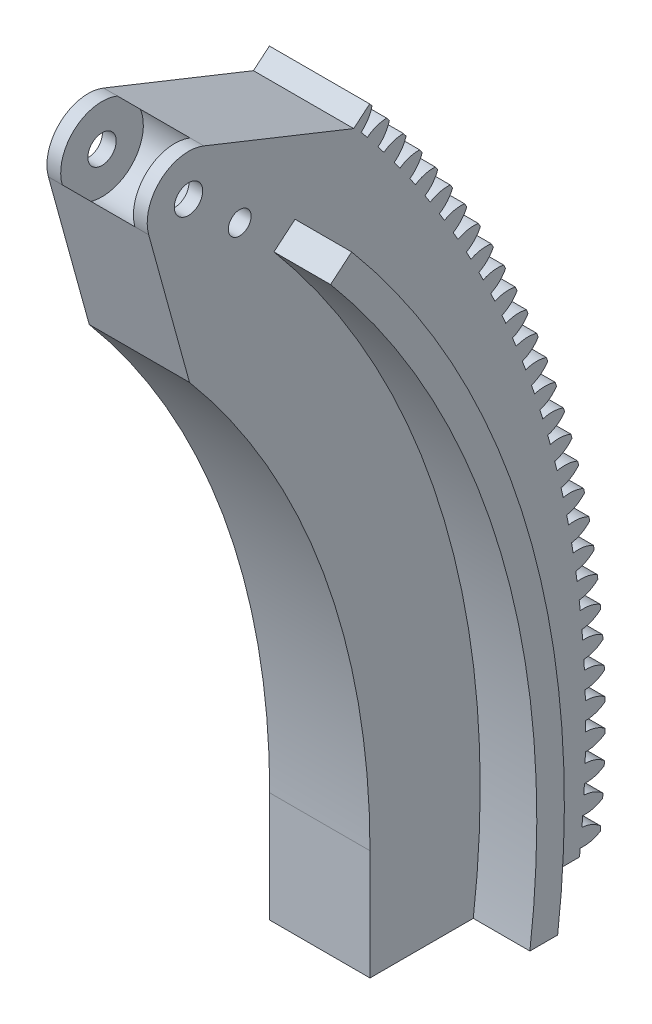
SolidWorks part; units mm, degrees
material "ABS"
ref_plane "Front Plane" through (0, 0, 0) normal (0, 0, 1) x (1, 0, 0)
ref_plane "Top Plane" through (0, 0, 0) normal (0, 1, 0) x (1, 0, 0)
ref_plane "Right Plane" through (0, 0, 0) normal (1, 0, 0) x (0, 0, -1)
ref_plane "idk" through (6.35, 0, 0) normal (1, 0, 0) x (0, 0, -1)
sketch "Sketch1" plane through (0, 0, 0) normal (1, 0, 0) x (0, 0, -1)
  line L0 (-1000, 0) -> (177.8, 0) construction
  line L1 (177.8, 0) -> (177.8, -25.4)
  line L2 (0, 0) -> (136.2027, 114.2876) construction
  line L4 (227.2, 0) -> (49000, 0) construction
  line L7 (177.8, -25.4) -> (227.2, -25.4) construction
  line L8 (227.2, 0) -> (227.2, -25.4) construction
  line L10 (-1.0719, -0.8495) -> (179.1555, 141.9904) construction
  line L61 (181.0098, 139.6187) -> (0, 0) construction
  line L62 (136.2027, 114.2876) -> (126.7844, 148.4774)
  line L64 (177.8, -25.4) -> (225.7757, -25.4)
  line L65 (136.2027, 114.2876) -> (155.124, 130.1645) construction
  line L66 (155.124, 130.1645) -> (174.0453, 146.0413) construction
  line L68 (0, 0) -> (35966.99, 34732.9185) construction
  line L69 (178.0587, 141.1212) -> (178.0836, 141.1409) construction
  line L70 (0, 0) -> (135.9673, 151.007) construction
  line L71 (139.5033, 159.8514) -> (174.0453, 146.0413)
  arc A2 (177.8, 0) -> (136.2027, 114.2876) centre (0, 0) ccw
  circle A19 centre (0, 0) radius 228.6 construction
  arc A22 (174.0453, 146.0413) -> (227.2, 0) centre (0, 0) cw
  arc A23 (227.2, 0) -> (225.7757, -25.4) centre (0, 0) cw
  arc A24 (126.7844, 148.4774) -> (139.5033, 159.8514) centre (135.9673, 151.007) cw
  point P6 (178.0836, 141.1409)
  point P7 (136.2027, 114.2876)
  dimension "D1" = 177.8
  dimension "D2" = 6.35
  dimension "D12" = 457.2
  dimension "D8" = 9.525
  dimension "D3" = 40
  dimension "D4" = 49.4
  dimension "D5" = 25.4
  dimension "D6" = 203.2
  dimension "D7" = 48
  dimension "D13" = 44
sketch "Sketch2" plane through (6.35, 0, 0) normal (1, 0, 0) x (0, 0, -1)
  line L0 (0, 0) -> (165.1, 0) construction
  line L1 (165.1, 0) -> (190.5, 0) construction
  line L2 (0, 0) -> (49240.3877, 8682.4089) construction
  circle A0 centre (165.1, 0) radius 3.2639
  circle A1 centre (190.5, 0) radius 3.2639
  arc A3 (165.1, 0) -> (162.5918, 28.6693) centre (0, 0) ccw construction
  circle A4 centre (162.5918, 28.6693) radius 3.2639
  arc A5 (190.5, 0) -> (187.6059, 33.08) centre (0, 0) ccw construction
  circle A6 centre (187.6059, 33.08) radius 3.2639
  dimension "D3" = 6.5278
  dimension "D4" = 6.5278
  dimension "D6" = 6.5278
  dimension "D7" = 6.5278
  dimension "D1" = 165.1
  dimension "D2" = 25.4
  dimension "D5" = 10
sketch "Sketch11" plane through (6.35, 0, 0) normal (1, 0, 0) x (0, 0, -1)
  line L0 (-785.502, -659.1144) -> (0, 0) construction
  line L2 (-1000, 0) -> (0, 0) construction
  line L4 (155.6602, 130.6144) -> (177.7223, 149.1267)
  line L5 (177.7223, 149.1267) -> (921.7047, 773.4021) construction
  line L6 (232, 0) -> (232, -25.4) construction
  line L7 (232, -25.4) -> (222.9391, -25.4) construction
  line L8 (201.6062, -25.4) -> (230.6054, -25.4)
  line L9 (203.2, 0) -> (232, 0) construction
  arc A0 (-230, 0) -> (-176.1902, -147.8412) centre (0, 0) ccw construction
  arc A1 (-232, 0) -> (-177.7223, -149.1267) centre (0, 0) ccw construction
  arc A2 (-229.6, 0) -> (-175.8838, -147.584) centre (0, 0) ccw construction
  arc A3 (232, 0) -> (177.7223, 149.1267) centre (0, 0) ccw
  arc A4 (230, 0) -> (176.1902, 147.8412) centre (0, 0) ccw construction
  arc A5 (-229.6, 0) -> (-175.8838, -147.584) centre (0, 0) ccw
  arc A6 (155.6602, 130.6144) -> (203.2, 0) centre (0, 0) cw
  arc A7 (232, 0) -> (230.6054, -25.4) centre (0, 0) cw
  arc A8 (203.2, 0) -> (201.6062, -25.4) centre (0, 0) cw
  dimension "D1" = 460
  dimension "D2" = 464
  dimension "D4" = 203.2
  dimension "D3" = 2.4
  dimension "D6" = 25.4
extrude "Teeth blank" add sketch "Sketch11" against normal blind 6.35 contours A3 L4 region at (6.35, 60.7212, -203.0048)
sketch "Sketch12" plane through (6.35, 0, 0) normal (1, 0, 0) x (0, 0, -1)
  line L0 (0, 0) -> (232, 0) construction
  line L2 (229.9946, 1.5708) -> (229.9946, -1.5708) construction
  line L3 (0, 0) -> (227.4972, 1.1241) construction
  line L4 (225.6789, 0) -> (232.9848, 2.6591) construction
  line L5 (0, 0) -> (232.9783, 3.1825) construction
  line L6 (229.9946, 1.5708) -> (229.9517, 4.7121) construction
  circle A0 centre (0, 0) radius 230 construction
  arc A1 (230.6054, -25.4) -> (177.7223, 149.1267) centre (0, 0) ccw construction
  circle A2 centre (0, 0) radius 227.5 construction
  arc A3 (227.4972, 1.1241) -> (232.9725, 3.5819) centre (227.4606, 8.5329) ccw
  arc A4 (231.5994, -25.5095) -> (232.9725, -3.5819) centre (0, 0) cw construction
  arc A5 (227.4972, -1.1241) -> (232.9725, -3.5819) centre (227.4606, -8.5329) cw
  arc A6 (231.5994, -25.5095) -> (178.4884, 149.7695) centre (0, 0) ccw
  arc A7 (231.5994, -25.5095) -> (232.9725, 3.5819) centre (0, 0) ccw construction
  arc A8 (227.4972, 1.1241) -> (227.4972, -1.1241) centre (0, 0) cw
  arc A9 (230.6054, -25.4) -> (177.7223, 149.1267) centre (0, 0) ccw construction
  arc A10 (232.9725, 3.5819) -> (232.9725, -3.5819) centre (0, 0) cw
  dimension "D1" = 460
  dimension "D3" = 20
  dimension "D4" = 0.783
  dimension "D5" = 4.5
  dimension "D2" = 1
extrude "Primary blank" add sketch "Sketch1" along normal blind 29.464
extrude "Tooth cut" cut sketch "Sketch12" against normal blind 6.35
pattern_circular "Tooth pattern" count 230 every 1.565 about axis through (0, 0, 0) along (1, 0, 0) of "Tooth cut"
sketch "Sketch15" plane through (6.35, 0, 0) normal (1, 0, 0) x (0, 0, -1)
  line L0 (0, 0) -> (135.9673, 151.007) construction
  line L2 (0, 0) -> (102.4673, 0) construction
  circle A0 centre (135.9673, 151.007) radius 3.2639
  dimension "D3" = 6.5278
  dimension "D1" = 203.2
  dimension "D2" = 48
extrude "Holes for top support" cut sketch "Sketch15" against normal through all both and the other way through all
sketch "Sketch22" plane through (6.35, 0, 0) normal (1, 0, 0) x (0, 0, -1)
  line L0 (0, 0) -> (135.9673, 151.007)
  line L1 (0, 0) -> (177.8, 0)
  dimension "D1" = 177.8
sketch "Sketch23" plane through (0, 0, 0) normal (1, 0, 0) x (0, 0, -1)
  line L0 (0, 0) -> (177.8, 0) construction
  line L1 (0, 0) -> (136.2027, 114.2876) construction
  line L2 (177.8, 0) -> (196.85, 0) construction
  line L3 (136.2027, 114.2876) -> (155.6602, 130.6144) construction
  line L5 (155.6602, 130.6144) -> (160.5246, 134.6961)
  line L7 (201.6062, -25.4) -> (0, 0) construction
  line L8 (208.0049, -25.4) -> (201.6062, -25.4)
  line L9 (177.8, -25.4) -> (226.0776, -25.4) construction
  arc A0 (177.8, 0) -> (136.2027, 114.2876) centre (0, 0) ccw construction
  circle A2 centre (196.85, 0) radius 6.35 construction
  arc A3 (203.2, 0) -> (155.6602, 130.6144) centre (0, 0) ccw
  arc A4 (209.55, 0) -> (160.5246, 134.6961) centre (0, 0) ccw
  circle A5 centre (215.9, 0) radius 6.35 construction
  arc A6 (203.2, 0) -> (201.6062, -25.4) centre (0, 0) cw
  arc A7 (209.55, 0) -> (208.0049, -25.4) centre (0, 0) cw
  dimension "D4" = 6.35
  dimension "D5" = 12.7
  dimension "D6" = 12.7
  dimension "D1" = 177.8
  dimension "D2" = 40
  dimension "D3" = 19.05
extrude "Thing to slide along bearings" add sketch "Sketch23" against normal blind 9.8742
ref_plane "Mirror plane" through (14.732, 0, 0) normal (1, 0, 0) x (0, 0, -1)
mirror "Mirroring slider" about plane through (14.732, 0, 0) normal (1, 0, 0) of "Thing to slide along bearings"
sketch "Sketch27" plane through (6.35, 0, 0) normal (1, 0, 0) x (0, 0, -1)
  line L2 (177.7223, 149.1267) -> (174.0453, 146.0413)
  line L3 (177.7223, 149.1267) -> (174.0453, 146.0413)
  line L7 (225.7757, -25.4) -> (226.0776, -25.4)
  line L8 (225.7757, -25.4) -> (226.0776, -25.4)
  arc A4 (227.2191, 11.3011) -> (227.0964, 13.5458) centre (0, 0) ccw
  arc A95 (231.8253, 9.0012) -> (231.7841, 10.0069) centre (0, 0) ccw
  arc A111 (227.3816, 7.3377) -> (231.8253, 9.0012) centre (227.1427, 14.7428) ccw
  arc A112 (227.3816, 7.3377) -> (231.8253, 9.0012) centre (227.1427, 14.7428) ccw
  arc A113 (231.7841, 10.0069) -> (227.2191, 11.3011) centre (227.5872, 3.9012) ccw
  arc A114 (231.7841, 10.0069) -> (227.2191, 11.3011) centre (227.5872, 3.9012) ccw
  arc A139 (227.2191, 11.3011) -> (227.0964, 13.5458) centre (0, 0) ccw
  arc A141 (227.0964, 13.5458) -> (231.493, 15.3301) centre (226.6552, 20.9417) ccw
  arc A143 (227.0964, 13.5458) -> (231.493, 15.3301) centre (226.6552, 20.9417) ccw
  arc A145 (231.493, 15.3301) -> (231.4243, 16.3343) centre (0, 0) ccw
  arc A147 (231.493, 15.3301) -> (231.4243, 16.3343) centre (0, 0) ccw
  arc A149 (231.4243, 16.3343) -> (226.8257, 17.5033) centre (227.3957, 10.1163) ccw
  arc A151 (231.4243, 16.3343) -> (226.8257, 17.5033) centre (227.3957, 10.1163) ccw
  arc A153 (226.8257, 17.5033) -> (226.6416, 19.7439) centre (0, 0) ccw
  arc A155 (226.8257, 17.5033) -> (226.6416, 19.7439) centre (0, 0) ccw
  arc A157 (226.6416, 19.7439) -> (230.9878, 21.6476) centre (225.9986, 27.1249) ccw
  arc A159 (226.6416, 19.7439) -> (230.9878, 21.6476) centre (225.9986, 27.1249) ccw
  arc A161 (230.9878, 21.6476) -> (230.8918, 22.6495) centre (0, 0) ccw
  arc A163 (230.9878, 21.6476) -> (230.8918, 22.6495) centre (0, 0) ccw
  arc A165 (230.8918, 22.6495) -> (226.2629, 23.6925) centre (227.0345, 16.3238) ccw
  arc A167 (230.8918, 22.6495) -> (226.2629, 23.6925) centre (227.0345, 16.3238) ccw
  arc A169 (226.2629, 23.6925) -> (226.0178, 25.9272) centre (0, 0) ccw
  arc A171 (226.2629, 23.6925) -> (226.0178, 25.9272) centre (0, 0) ccw
  arc A173 (226.0178, 25.9272) -> (230.3104, 27.9489) centre (225.1734, 33.2879) ccw
  arc A175 (226.0178, 25.9272) -> (230.3104, 27.9489) centre (225.1734, 33.2879) ccw
  arc A177 (230.3104, 27.9489) -> (230.1869, 28.9478) centre (0, 0) ccw
  arc A179 (230.3104, 27.9489) -> (230.1869, 28.9478) centre (0, 0) ccw
  arc A181 (230.1869, 28.9478) -> (225.5314, 29.8639) centre (226.5039, 22.5191) ccw
  arc A182 (230.1869, 28.9478) -> (225.5314, 29.8639) centre (226.5039, 22.5191) ccw
  arc A184 (225.5314, 29.8639) -> (225.2252, 32.0911) centre (0, 0) ccw
  arc A186 (225.5314, 29.8639) -> (225.2252, 32.0911) centre (0, 0) ccw
  arc A189 (231.8253, 9.0012) -> (231.7841, 10.0069) centre (0, 0) ccw
  arc A282 (225.2252, 32.0911) -> (229.461, 34.2294) centre (224.1801, 39.426) ccw
  arc A284 (225.2252, 32.0911) -> (229.461, 34.2294) centre (224.1801, 39.426) ccw
  arc A286 (229.461, 34.2294) -> (229.3104, 35.2245) centre (0, 0) ccw
  arc A288 (229.461, 34.2294) -> (229.3104, 35.2245) centre (0, 0) ccw
  arc A290 (229.3104, 35.2245) -> (224.6315, 36.0131) centre (225.8043, 28.6976) ccw
  arc A292 (229.3104, 35.2245) -> (224.6315, 36.0131) centre (225.8043, 28.6976) ccw
  arc A294 (224.6315, 36.0131) -> (224.2647, 38.2311) centre (0, 0) ccw
  arc A296 (224.6315, 36.0131) -> (224.2647, 38.2311) centre (0, 0) ccw
  arc A298 (224.2647, 38.2311) -> (228.4404, 40.4843) centre (223.0196, 45.5347) ccw
  arc A300 (224.2647, 38.2311) -> (228.4404, 40.4843) centre (223.0196, 45.5347) ccw
  arc A302 (228.4404, 40.4843) -> (228.2626, 41.4749) centre (0, 0) ccw
  arc A304 (228.4404, 40.4843) -> (228.2626, 41.4749) centre (0, 0) ccw
  arc A306 (228.2626, 41.4749) -> (223.564, 42.1355) centre (224.9362, 34.8547) ccw
  arc A308 (228.2626, 41.4749) -> (223.564, 42.1355) centre (224.9362, 34.8547) ccw
  arc A310 (223.564, 42.1355) -> (223.1367, 44.3426) centre (0, 0) ccw
  arc A312 (223.564, 42.1355) -> (223.1367, 44.3426) centre (0, 0) ccw
  arc A314 (223.1367, 44.3426) -> (227.2494, 46.709) centre (221.6926, 51.6095) ccw
  arc A316 (223.1367, 44.3426) -> (227.2494, 46.709) centre (221.6926, 51.6095) ccw
  arc A318 (227.2494, 46.709) -> (227.0446, 47.6944) centre (0, 0) ccw
  arc A320 (227.2494, 46.709) -> (227.0446, 47.6944) centre (0, 0) ccw
  arc A322 (227.0446, 47.6944) -> (222.3296, 48.2264) centre (223.9002, 40.9858) ccw
  arc A324 (227.0446, 47.6944) -> (222.3296, 48.2264) centre (223.9002, 40.9858) ccw
  arc A326 (222.3296, 48.2264) -> (221.8422, 50.421) centre (0, 0) ccw
  arc A328 (222.3296, 48.2264) -> (221.8422, 50.421) centre (0, 0) ccw
  arc A330 (221.8422, 50.421) -> (225.8887, 52.8988) centre (220.2002, 57.6457) ccw
  arc A332 (221.8422, 50.421) -> (225.8887, 52.8988) centre (220.2002, 57.6457) ccw
  arc A334 (225.8887, 52.8988) -> (225.6571, 53.8783) centre (0, 0) ccw
  arc A336 (225.8887, 52.8988) -> (225.6571, 53.8783) centre (0, 0) ccw
  arc A338 (225.6571, 53.8783) -> (220.9294, 54.2813) centre (222.6972, 47.0863) ccw
  arc A340 (225.6571, 53.8783) -> (220.9294, 54.2813) centre (222.6972, 47.0863) ccw
  arc A342 (220.9294, 54.2813) -> (220.3822, 56.4618) centre (0, 0) ccw
  arc A344 (220.9294, 54.2813) -> (220.3822, 56.4618) centre (0, 0) ccw
  arc A346 (220.3822, 56.4618) -> (224.3595, 59.0492) centre (218.5434, 63.6389) ccw
  arc A348 (220.3822, 56.4618) -> (224.3595, 59.0492) centre (218.5434, 63.6389) ccw
  arc A350 (224.3595, 59.0492) -> (224.1012, 60.022) centre (0, 0) ccw
  arc A352 (224.3595, 59.0492) -> (224.1012, 60.022) centre (0, 0) ccw
  arc A354 (224.1012, 60.022) -> (219.3643, 60.2956) centre (221.3279, 53.1516) ccw
  arc A356 (224.1012, 60.022) -> (219.3643, 60.2956) centre (221.3279, 53.1516) ccw
  arc A358 (219.3643, 60.2956) -> (218.7577, 62.4604) centre (0, 0) ccw
  arc A360 (219.3643, 60.2956) -> (218.7577, 62.4604) centre (0, 0) ccw
  arc A362 (218.7577, 62.4604) -> (222.6629, 65.1555) centre (216.7236, 69.5847) ccw
  arc A364 (218.7577, 62.4604) -> (222.6629, 65.1555) centre (216.7236, 69.5847) ccw
  arc A366 (222.6629, 65.1555) -> (222.3781, 66.1209) centre (0, 0) ccw
  arc A368 (222.6629, 65.1555) -> (222.3781, 66.1209) centre (0, 0) ccw
  arc A370 (222.3781, 66.1209) -> (217.6355, 66.265) centre (219.7935, 59.1773) ccw
  arc A372 (222.3781, 66.1209) -> (217.6355, 66.265) centre (219.7935, 59.1773) ccw
  arc A374 (217.6355, 66.265) -> (216.97, 68.4124) centre (0, 0) ccw
  arc A376 (217.6355, 66.265) -> (216.97, 68.4124) centre (0, 0) ccw
  arc A378 (216.97, 68.4124) -> (220.8001, 71.2132) centre (214.742, 75.4785) ccw
  arc A380 (216.97, 68.4124) -> (220.8001, 71.2132) centre (214.742, 75.4785) ccw
  arc A382 (220.8001, 71.2132) -> (220.4891, 72.1704) centre (0, 0) ccw
  arc A384 (220.8001, 71.2132) -> (220.4891, 72.1704) centre (0, 0) ccw
  arc A386 (220.4891, 72.1704) -> (215.7443, 72.185) centre (218.0951, 65.1589) ccw
  arc A388 (220.4891, 72.1704) -> (215.7443, 72.185) centre (218.0951, 65.1589) ccw
  arc A390 (215.7443, 72.185) -> (215.0204, 74.3134) centre (0, 0) ccw
  arc A394 (215.7443, 72.185) -> (215.0204, 74.3134) centre (0, 0) ccw
  arc A398 (215.0204, 74.3134) -> (218.7726, 77.2177) centre (212.6002, 81.3159) ccw
  arc A402 (215.0204, 74.3134) -> (218.7726, 77.2177) centre (212.6002, 81.3159) ccw
  arc A406 (218.7726, 77.2177) -> (218.4355, 78.1661) centre (0, 0) ccw
  arc A410 (218.7726, 77.2177) -> (218.4355, 78.1661) centre (0, 0) ccw
  arc A414 (218.4355, 78.1661) -> (213.692, 78.0511) centre (216.2339, 71.0918) ccw
  arc A418 (218.4355, 78.1661) -> (213.692, 78.0511) centre (216.2339, 71.0918) ccw
  arc A420 (213.692, 78.0511) -> (212.9103, 80.1589) centre (0, 0) ccw
  arc A422 (213.692, 78.0511) -> (212.9103, 80.1589) centre (0, 0) ccw
  arc A423 (212.9103, 80.1589) -> (216.5817, 83.1646) centre (210.2998, 87.0927) ccw
  arc A424 (212.9103, 80.1589) -> (216.5817, 83.1646) centre (210.2998, 87.0927) ccw
  arc A425 (216.5817, 83.1646) -> (216.2189, 84.1034) centre (0, 0) ccw
  arc A426 (216.5817, 83.1646) -> (216.2189, 84.1034) centre (0, 0) ccw
  arc A427 (216.2189, 84.1034) -> (211.4804, 83.8589) centre (214.2114, 76.9716) ccw
  arc A428 (216.2189, 84.1034) -> (211.4804, 83.8589) centre (214.2114, 76.9716) ccw
  arc A429 (211.4804, 83.8589) -> (210.6414, 85.9446) centre (0, 0) ccw
  arc A430 (211.4804, 83.8589) -> (210.6414, 85.9446) centre (0, 0) ccw
  arc A431 (210.6414, 85.9446) -> (214.2293, 89.0495) centre (207.8424, 92.8045) ccw
  arc A432 (210.6414, 85.9446) -> (214.2293, 89.0495) centre (207.8424, 92.8045) ccw
  arc A434 (214.2293, 89.0495) -> (213.841, 89.978) centre (0, 0) ccw
  arc A436 (214.2293, 89.0495) -> (213.841, 89.978) centre (0, 0) ccw
  arc A438 (213.841, 89.978) -> (209.1109, 89.6041) centre (212.029, 82.794) ccw
  arc A440 (213.841, 89.978) -> (209.1109, 89.6041) centre (212.029, 82.794) ccw
  arc A442 (209.1109, 89.6041) -> (208.2152, 91.6661) centre (0, 0) ccw
  arc A444 (209.1109, 89.6041) -> (208.2152, 91.6661) centre (0, 0) ccw
  arc A446 (208.2152, 91.6661) -> (211.717, 94.8679) centre (205.2299, 98.4471) ccw
  arc A448 (208.2152, 91.6661) -> (211.717, 94.8679) centre (205.2299, 98.4471) ccw
  arc A450 (211.717, 94.8679) -> (211.3034, 95.7855) centre (0, 0) ccw
  arc A452 (211.717, 94.8679) -> (211.3034, 95.7855) centre (0, 0) ccw
  arc A454 (211.3034, 95.7855) -> (206.5853, 95.2825) centre (209.6884, 88.5547) ccw
  arc A456 (211.3034, 95.7855) -> (206.5853, 95.2825) centre (209.6884, 88.5547) ccw
  arc A458 (206.5853, 95.2825) -> (205.6337, 97.3193) centre (0, 0) ccw
  arc A460 (206.5853, 95.2825) -> (205.6337, 97.3193) centre (0, 0) ccw
  arc A462 (205.6337, 97.3193) -> (209.0467, 100.6155) centre (202.4643, 104.0162) ccw
  arc A464 (205.6337, 97.3193) -> (209.0467, 100.6155) centre (202.4643, 104.0162) ccw
  arc A466 (209.0467, 100.6155) -> (208.6082, 101.5215) centre (0, 0) ccw
  arc A467 (209.0467, 100.6155) -> (208.6082, 101.5215) centre (0, 0) ccw
  arc A468 (208.6082, 101.5215) -> (203.9056, 100.8898) centre (207.1913, 94.2492) ccw
  arc A469 (208.6082, 101.5215) -> (203.9056, 100.8898) centre (207.1913, 94.2492) ccw
  arc A470 (203.9056, 100.8898) -> (202.8987, 102.8998) centre (0, 0) ccw
  arc A471 (203.9056, 100.8898) -> (202.8987, 102.8998) centre (0, 0) ccw
  arc A472 (202.8987, 102.8998) -> (206.2204, 106.288) centre (199.5476, 109.5076) ccw
  arc A473 (202.8987, 102.8998) -> (206.2204, 106.288) centre (199.5476, 109.5076) ccw
  arc A474 (206.2204, 106.288) -> (205.7574, 107.1817) centre (0, 0) ccw
  arc A475 (206.2204, 106.288) -> (205.7574, 107.1817) centre (0, 0) ccw
  arc A476 (205.7574, 107.1817) -> (201.0737, 106.4218) centre (204.5396, 99.8735) ccw
  arc A477 (205.7574, 107.1817) -> (201.0737, 106.4218) centre (204.5396, 99.8735) ccw
  arc A478 (201.0737, 106.4218) -> (200.0123, 108.4036) centre (0, 0) ccw
  arc A479 (201.0737, 106.4218) -> (200.0123, 108.4036) centre (0, 0) ccw
  arc A480 (200.0123, 108.4036) -> (203.2402, 111.8812) centre (196.4819, 114.9174) ccw
  arc A481 (200.0123, 108.4036) -> (203.2402, 111.8812) centre (196.4819, 114.9174) ccw
  arc A482 (203.2402, 111.8812) -> (202.7529, 112.7619) centre (0, 0) ccw
  arc A483 (203.2402, 111.8812) -> (202.7529, 112.7619) centre (0, 0) ccw
  arc A484 (202.7529, 112.7619) -> (198.0918, 111.8744) centre (201.7352, 105.4232) ccw
  arc A485 (202.7529, 112.7619) -> (198.0918, 111.8744) centre (201.7352, 105.4232) ccw
  arc A486 (198.0918, 111.8744) -> (196.9766, 113.8264) centre (0, 0) ccw
  arc A487 (198.0918, 111.8744) -> (196.9766, 113.8264) centre (0, 0) ccw
  arc A488 (196.9766, 113.8264) -> (200.1084, 117.3909) centre (193.2697, 120.2413) ccw
  arc A489 (196.9766, 113.8264) -> (200.1084, 117.3909) centre (193.2697, 120.2413) ccw
  arc A490 (200.1084, 117.3909) -> (199.5972, 118.258) centre (0, 0) ccw
  arc A491 (200.1084, 117.3909) -> (199.5972, 118.258) centre (0, 0) ccw
  arc A492 (199.5972, 118.258) -> (194.9621, 117.2435) centre (198.7804, 110.8942) ccw
  arc A493 (199.5972, 118.258) -> (194.9621, 117.2435) centre (198.7804, 110.8942) ccw
  arc A494 (194.9621, 117.2435) -> (193.794, 119.1643) centre (0, 0) ccw
  arc A495 (194.9621, 117.2435) -> (193.794, 119.1643) centre (0, 0) ccw
  arc A496 (193.794, 119.1643) -> (196.8272, 122.8131) centre (189.9132, 125.4756) ccw
  arc A497 (193.794, 119.1643) -> (196.8272, 122.8131) centre (189.9132, 125.4756) ccw
  arc A498 (196.8272, 122.8131) -> (196.2926, 123.6658) centre (0, 0) ccw
  arc A499 (196.8272, 122.8131) -> (196.2926, 123.6658) centre (0, 0) ccw
  arc A500 (196.2926, 123.6658) -> (191.6869, 122.5251) centre (195.6771, 116.2824) ccw
  arc A501 (196.2926, 123.6658) -> (191.6869, 122.5251) centre (195.6771, 116.2824) ccw
  arc A502 (191.6869, 122.5251) -> (190.4667, 124.4133) centre (0, 0) ccw
  arc A503 (191.6869, 122.5251) -> (190.4667, 124.4133) centre (0, 0) ccw
  arc A504 (190.4667, 124.4133) -> (193.3992, 128.1435) centre (186.415, 130.6162) ccw
  arc A505 (190.4667, 124.4133) -> (193.3992, 128.1435) centre (186.415, 130.6162) ccw
  arc A506 (193.3992, 128.1435) -> (192.8414, 128.9814) centre (0, 0) ccw
  arc A507 (193.3992, 128.1435) -> (192.8414, 128.9814) centre (0, 0) ccw
  arc A508 (192.8414, 128.9814) -> (188.2686, 127.7153) centre (192.4279, 121.5839) ccw
  arc A509 (192.8414, 128.9814) -> (188.2686, 127.7153) centre (192.4279, 121.5839) ccw
  arc A510 (188.2686, 127.7153) -> (186.9974, 129.5694) centre (0, 0) ccw
  arc A511 (188.2686, 127.7153) -> (186.9974, 129.5694) centre (0, 0) ccw
  arc A512 (186.9974, 129.5694) -> (189.8268, 133.3784) centre (182.7777, 135.6594) ccw
  arc A513 (186.9974, 129.5694) -> (189.8268, 133.3784) centre (182.7777, 135.6594) ccw
  arc A514 (189.8268, 133.3784) -> (189.2464, 134.2007) centre (0, 0) ccw
  arc A515 (189.8268, 133.3784) -> (189.2464, 134.2007) centre (0, 0) ccw
  arc A516 (189.2464, 134.2007) -> (184.7098, 132.8101) centre (189.0351, 126.7947) ccw
  arc A517 (189.2464, 134.2007) -> (184.7098, 132.8101) centre (189.0351, 126.7947) ccw
  arc A518 (184.7098, 132.8101) -> (183.3884, 134.6289) centre (0, 0) ccw
  arc A519 (184.7098, 132.8101) -> (183.3884, 134.6289) centre (0, 0) ccw
  arc A520 (225.7757, -25.4) -> (174.0453, 146.0413) centre (0, 0) ccw
  arc A521 (225.7757, -25.4) -> (174.0453, 146.0413) centre (0, 0) ccw
  arc A522 (227.4972, -1.1241) -> (227.4972, 1.1241) centre (0, 0) ccw
  arc A523 (227.4972, -1.1241) -> (227.4972, 1.1241) centre (0, 0) ccw
  arc A524 (227.4972, 1.1241) -> (231.9847, 2.6656) centre (227.4606, 8.5329) ccw
  arc A525 (227.4972, 1.1241) -> (231.9847, 2.6656) centre (227.4606, 8.5329) ccw
  arc A526 (231.9847, 2.6656) -> (231.9709, 3.672) centre (0, 0) ccw
  arc A527 (231.9847, 2.6656) -> (231.9709, 3.672) centre (0, 0) ccw
  arc A528 (231.9709, 3.672) -> (227.4431, 5.0904) centre (227.6088, -2.3167) ccw
  arc A529 (231.9709, 3.672) -> (227.4431, 5.0904) centre (227.6088, -2.3167) ccw
  arc A530 (227.4431, 5.0904) -> (227.3816, 7.3377) centre (0, 0) ccw
  arc A531 (227.4431, 5.0904) -> (227.3816, 7.3377) centre (0, 0) ccw
  arc A532 (231.9709, -3.672) -> (231.9847, -2.6656) centre (0, 0) ccw
  arc A533 (231.9709, -3.672) -> (231.9847, -2.6656) centre (0, 0) ccw
  arc A534 (231.9847, -2.6656) -> (227.4972, -1.1241) centre (227.4606, -8.5329) ccw
  arc A535 (231.9847, -2.6656) -> (227.4972, -1.1241) centre (227.4606, -8.5329) ccw
  arc A536 (183.3884, 134.6289) -> (186.1128, 138.5137) centre (179.004, 140.6013) ccw
  arc A537 (183.3884, 134.6289) -> (186.1128, 138.5137) centre (179.004, 140.6013) ccw
  arc A538 (186.1128, 138.5137) -> (185.5101, 139.3198) centre (0, 0) ccw
  arc A539 (186.1128, 138.5137) -> (185.5101, 139.3198) centre (0, 0) ccw
  arc A540 (185.5101, 139.3198) -> (181.0132, 137.8059) centre (185.5011, 131.9108) ccw
  arc A541 (185.5101, 139.3198) -> (181.0132, 137.8059) centre (185.5011, 131.9108) ccw
  arc A542 (181.0132, 137.8059) -> (179.6426, 139.5879) centre (0, 0) ccw
  arc A543 (181.0132, 137.8059) -> (179.6426, 139.5879) centre (0, 0) ccw
  arc A544 (179.6426, 139.5879) -> (182.2598, 143.5456) centre (175.0967, 145.4383) ccw
  arc A545 (179.6426, 139.5879) -> (182.2598, 143.5456) centre (175.0967, 145.4383) ccw
  arc A546 (182.2598, 143.5456) -> (181.6354, 144.335) centre (0, 0) ccw
  arc A547 (182.2598, 143.5456) -> (181.6354, 144.335) centre (0, 0) ccw
  arc A548 (181.6354, 144.335) -> (177.1815, 142.6988) centre (181.8288, 136.9286) ccw
  arc A549 (181.6354, 144.335) -> (177.1815, 142.6988) centre (181.8288, 136.9286) ccw
  arc A550 (177.1815, 142.6988) -> (175.7628, 144.4427) centre (0, 0) ccw
  arc A551 (177.1815, 142.6988) -> (175.7628, 144.4427) centre (0, 0) ccw
  arc A552 (175.7628, 144.4427) -> (178.2709, 148.4705) centre (171.0587, 150.1668) ccw
  arc A553 (175.7628, 144.4427) -> (178.2709, 148.4705) centre (171.0587, 150.1668) ccw
  arc A554 (178.2709, 148.4705) -> (177.7223, 149.1267) centre (0, 0) ccw
  arc A555 (178.2709, 148.4705) -> (177.7223, 149.1267) centre (0, 0) ccw
  arc A556 (226.0776, -25.4) -> (226.2629, -23.6925) centre (0, 0) ccw
  arc A557 (226.0776, -25.4) -> (226.2629, -23.6925) centre (0, 0) ccw
  arc A558 (226.2629, -23.6925) -> (230.8918, -22.6495) centre (227.0345, -16.3238) ccw
  arc A559 (226.2629, -23.6925) -> (230.8918, -22.6495) centre (227.0345, -16.3238) ccw
  arc A560 (230.8918, -22.6495) -> (230.9878, -21.6476) centre (0, 0) ccw
  arc A561 (230.8918, -22.6495) -> (230.9878, -21.6476) centre (0, 0) ccw
  arc A562 (230.9878, -21.6476) -> (226.6416, -19.7439) centre (225.9986, -27.1249) ccw
  arc A563 (230.9878, -21.6476) -> (226.6416, -19.7439) centre (225.9986, -27.1249) ccw
  arc A564 (226.6416, -19.7439) -> (226.8257, -17.5033) centre (0, 0) ccw
  arc A565 (226.6416, -19.7439) -> (226.8257, -17.5033) centre (0, 0) ccw
  arc A566 (226.8257, -17.5033) -> (231.4243, -16.3343) centre (227.3957, -10.1163) ccw
  arc A567 (226.8257, -17.5033) -> (231.4243, -16.3343) centre (227.3957, -10.1163) ccw
  arc A568 (231.4243, -16.3343) -> (231.493, -15.3301) centre (0, 0) ccw
  arc A569 (231.4243, -16.3343) -> (231.493, -15.3301) centre (0, 0) ccw
  arc A570 (231.493, -15.3301) -> (227.0964, -13.5458) centre (226.6552, -20.9417) ccw
  arc A571 (231.493, -15.3301) -> (227.0964, -13.5458) centre (226.6552, -20.9417) ccw
  arc A572 (227.0964, -13.5458) -> (227.2191, -11.3011) centre (0, 0) ccw
  arc A573 (227.0964, -13.5458) -> (227.2191, -11.3011) centre (0, 0) ccw
  arc A574 (227.2191, -11.3011) -> (231.7841, -10.0069) centre (227.5872, -3.9012) ccw
  arc A575 (227.2191, -11.3011) -> (231.7841, -10.0069) centre (227.5872, -3.9012) ccw
  arc A576 (231.7841, -10.0069) -> (231.8253, -9.0012) centre (0, 0) ccw
  arc A577 (231.7841, -10.0069) -> (231.8253, -9.0012) centre (0, 0) ccw
  arc A578 (231.8253, -9.0012) -> (227.3816, -7.3377) centre (227.1427, -14.7428) ccw
  arc A579 (231.8253, -9.0012) -> (227.3816, -7.3377) centre (227.1427, -14.7428) ccw
  arc A580 (227.3816, -7.3377) -> (227.4431, -5.0904) centre (0, 0) ccw
  arc A581 (227.3816, -7.3377) -> (227.4431, -5.0904) centre (0, 0) ccw
  arc A582 (227.4431, -5.0904) -> (231.9709, -3.672) centre (227.6088, 2.3167) ccw
  arc A583 (227.4431, -5.0904) -> (231.9709, -3.672) centre (227.6088, 2.3167) ccw
  dimension "D1" = 0
extrude "Extending teeth" add sketch "Sketch27" along normal blind 23.0187
ref_plane "Plane for cut for space for top support screws" through (6.35, 0, 0) normal (-1, 0, 0) x (0, 0, 1)
sketch "Sketch28" plane through (6.35, 0, 0) normal (1, 0, 0) x (0, 0, -1)
  circle A0 centre (135.9673, 151.007) radius 9.525
  arc A1 (139.5033, 159.8514) -> (126.7844, 148.4774) centre (135.9673, 151.007) ccw construction
extrude "Cut for space for top support screws" cut sketch "Sketch28" along normal blind 16.764
sketch "Sketch29" plane through (0, -25.4, 0) normal (0, -1, 0) x (1, 0, 0)
  line L0 (14.6844, -226.0776) -> (14.732, -177.8) construction
  line L1 (29.3687, -226.0776) -> (0, -226.0776) construction
  line L2 (29.464, -177.8) -> (0, -177.8) construction
  circle A0 centre (14.7082, -201.9388) radius 3.429
  dimension "D1" = 6.858
extrude "Magnet hole" cut sketch "Sketch29" against normal blind 12.7
sketch "Sketch30" plane through (29.464, 0, 0) normal (1, 0, 0) x (0, 0, -1)
  line L0 (174.0453, 146.0413) -> (183.7741, 154.2047)
  line L1 (225.7757, -25.4) -> (238.5516, -25.4)
  line L6 (155.6602, 130.6144) -> (160.5246, 134.6961)
  line L7 (208.0049, -25.4) -> (225.7757, -25.4)
  line L8 (174.0453, 146.0413) -> (139.5033, 159.8514)
  line L9 (126.7844, 148.4774) -> (136.2027, 114.2876)
  line L10 (177.8, 0) -> (177.8, -25.4)
  line L11 (177.8, -25.4) -> (201.6062, -25.4)
  line L12 (155.6602, 130.6144) -> (160.5246, 134.6961)
  line L13 (208.0049, -25.4) -> (225.7757, -25.4)
  line L14 (174.0453, 146.0413) -> (139.5033, 159.8514)
  line L15 (126.7844, 148.4774) -> (136.2027, 114.2876)
  line L16 (177.8, 0) -> (177.8, -25.4)
  line L17 (177.8, -25.4) -> (201.6062, -25.4)
  arc A0 (183.7741, 154.2047) -> (238.5516, -25.4) centre (0, 0) cw
  arc A5 (201.6062, -25.4) -> (155.6602, 130.6144) centre (0, 0) ccw
  arc A6 (208.0049, -25.4) -> (160.5246, 134.6961) centre (0, 0) ccw
  arc A7 (225.7757, -25.4) -> (174.0453, 146.0413) centre (0, 0) ccw
  arc A8 (139.5033, 159.8514) -> (126.7844, 148.4774) centre (135.9673, 151.007) ccw
  arc A9 (177.8, 0) -> (136.2027, 114.2876) centre (0, 0) ccw
  arc A10 (201.6062, -25.4) -> (155.6602, 130.6144) centre (0, 0) ccw
  arc A11 (208.0049, -25.4) -> (160.5246, 134.6961) centre (0, 0) ccw
  arc A12 (225.7757, -25.4) -> (174.0453, 146.0413) centre (0, 0) ccw construction
  arc A13 (139.5033, 159.8514) -> (126.7844, 148.4774) centre (135.9673, 151.007) ccw
  arc A14 (177.8, 0) -> (136.2027, 114.2876) centre (0, 0) ccw
  dimension "D2" = 12.7
  dimension "D1" = 0
extrude "Cut to make space for aluminum reinforcement plate" cut sketch "Sketch30" against normal blind 3.175
mirror "Mirroring the above cut" about plane through (14.732, 0, 0) normal (1, 0, 0) of "Cut to make space for aluminum reinforcement plate"
sketch "Sketch31" plane through (3.175, 0, 0) normal (-1, 0, 0) x (0, 0, 1)
  line L0 (-135.9673, 151.007) -> (-147.7648, 140.3846) construction
  line L1 (-135.9673, 151.007) -> (0, 0) construction
  circle A0 centre (-147.7648, 140.3846) radius 2.6289
  dimension "D2" = 5.2578
  dimension "D1" = 15.875
extrude "Cut-Extrude1" cut sketch "Sketch31" against normal through all
equation "\"Module\"= 2mm"
equation "\"Number of Teeth\"= 230"
equation "\"D1@Sketch12\"=\"Module\" * \"Number of Teeth\""
equation "\"D4@Sketch12\"=180 / \"Number of Teeth\""
equation "\"D2\"= 360 / \"Number of Teeth\""
equation "\"D2@Sketch11\"=( \"Number of Teeth\" + 2) * \"Module\""
equation "\"D2@Tooth pattern\" = 360 / \"Number of Teeth\""
equation "\"D5@Sketch12\"= 2.25 * \"Module\""
equation "\"D1@Tooth pattern\" = \"Number of Teeth\""
